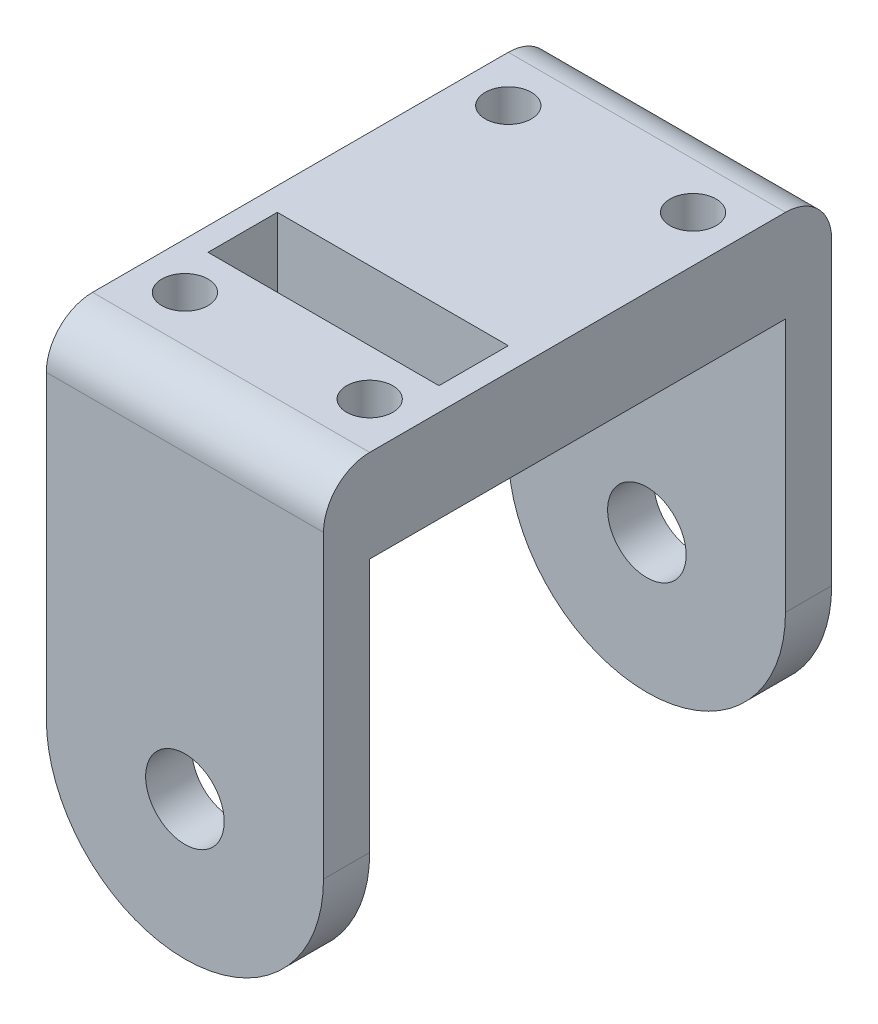
SolidWorks part; units mm, degrees
ref_plane "Front Plane" through (0, 0, 0) normal (0, 0, 1) x (1, 0, 0)
ref_plane "Top Plane" through (0, 0, 0) normal (0, 1, 0) x (1, 0, 0)
ref_plane "Right Plane" through (0, 0, 0) normal (1, 0, 0) x (0, 0, -1)
sketch "Sketch1" plane through (0, 0, 0) normal (0, 1, 0) x (1, 0, 0)
  line L1 (-30, 45) -> (30, 45)
  line L2 (-30, 45) -> (-30, -45)
  line L3 (-30, -45) -> (30, -45)
  line L4 (30, 45) -> (30, -45)
  line L5 (-30, 45) -> (30, -45) construction
  line L6 (-30, -45) -> (30, 45) construction
  point P0 (0, 0)
  dimension "D1" = 90
  dimension "D2" = 60
extrude "Boss-Extrude1" add sketch "Sketch1" along normal blind 20
sketch "Sketch3" plane through (0, 20, 0) normal (0, 1, 0) x (1, 0, 0)
  line L0 (0, -32.6793) -> (0, 38.6766) construction
  line L1 (-73.559, 0) -> (75.1615, 0) construction
  line L2 (20, -35) -> (20, 35)
  line L5 (20, 35) -> (-20, 35)
  line L6 (-20, 35) -> (-20, -35)
  line L7 (-20, -35) -> (20, -35)
  line L8 (30, -45) -> (30, 45)
  line L9 (30, 45) -> (-30, 45)
  line L10 (-30, 45) -> (-30, -45)
  line L11 (-30, -45) -> (30, -45)
  line L12 (30, -45) -> (30, 45)
  line L13 (30, 45) -> (-30, 45)
  line L14 (-30, 45) -> (-30, -45)
  line L15 (-30, -45) -> (30, -45)
  circle A0 centre (-20, 35) radius 5
  circle A1 centre (20, 35) radius 5
  circle A2 centre (20, -35) radius 5
  circle A3 centre (-20, -35) radius 5
  point P13 (0, 0)
  dimension "D3" = 10
  dimension "D4" = 0
  dimension "D5" = 10
extrude "Cut-Extrude1" cut sketch "Sketch3" against normal blind 10 contours L5 A0 L6 | L6 A0 L5 | L6 A3 L7 | L7 A3 L6 | L7 A2 L2 | L2 A2 L7 | L2 A1 L5 | L5 A1 L2 region at (17.8779, 20, 32.8779) region at (20.7074, 20, 35.7074) region at (17.8779, 20, -32.8779) region at (20.7074, 20, -35.7074) region at (-20.7074, 20, 35.7074) region at (-17.8779, 20, 32.8779) region at (-17.8779, 20, -32.8779) region at (-20.7074, 20, -35.7074)
sketch "Sketch4" plane through (0, 0, 45) normal (0, 0, 1) x (1, 0, 0)
  line L0 (0, 25.7358) -> (0, -90.3015) construction
  line L3 (-30, 0) -> (-30, -55)
  line L5 (30, -55) -> (30, 0)
  line L12 (-30, 0) -> (30, 0)
  line L13 (30, 0) -> (30, 20)
  line L14 (30, 20) -> (-30, 20)
  line L15 (-30, 20) -> (-30, 0)
  line L17 (30, 0) -> (30, 20)
  line L18 (30, 20) -> (-30, 20)
  line L19 (-30, 20) -> (-30, 0)
  arc A0 (30, -55) -> (-30, -55) centre (0, -55) cw
  dimension "D2" = 75
  dimension "D1" = 0
extrude "Boss-Extrude2" add sketch "Sketch4" along normal blind 10
mirror "Mirror1" about plane through (0, 0, 0) normal (0, 0, 1) of "Boss-Extrude2"
sketch "Sketch5" plane through (0, 0, 55) normal (0, 0, 1) x (1, 0, 0)
  circle A0 centre (0, -55) radius 8.5
  arc A1 (-30, -55) -> (30, -55) centre (0, -55) ccw construction
  arc A2 (-30, -55) -> (30, -55) centre (0, -55) ccw
  point P8 (0, 0)
  point P9 (0, 0)
  dimension "D1" = 17
extrude "Cut-Extrude2" cut sketch "Sketch5" against normal through all contours A0
fillet "Fillet1" radius 10 2 edges at (0, 20, -55) (0, 20, 55)
sketch "Sketch6" plane through (0, 20, 0) normal (0, 1, 0) x (1, 0, 0)
  line L0 (-30, -55) -> (-30, -25) construction
  line L1 (-30, 45) -> (-30, -45) construction
  line L2 (30, -45) -> (30, 45) construction
  line L3 (-30, -25) -> (30, -25)
  line L4 (-30, -25) -> (-30, -10)
  line L5 (-30, -10) -> (30, -10)
  line L6 (30, -25) -> (30, -10)
  line L7 (-25, -10) -> (-25, -25)
  line L8 (25, -10) -> (25, -25)
  dimension "D1" = 30
  dimension "D2" = 15
  dimension "D3" = 5
  dimension "D4" = 5
extrude "Cut-Extrude3" cut sketch "Sketch6" against normal through all contours L8 L5 L7 L3 region at (0, 20, 17.5)
fillet "Fillet2" radius 5 2 edges at (-25, 0, 17.5) (25, 0, 17.5)
